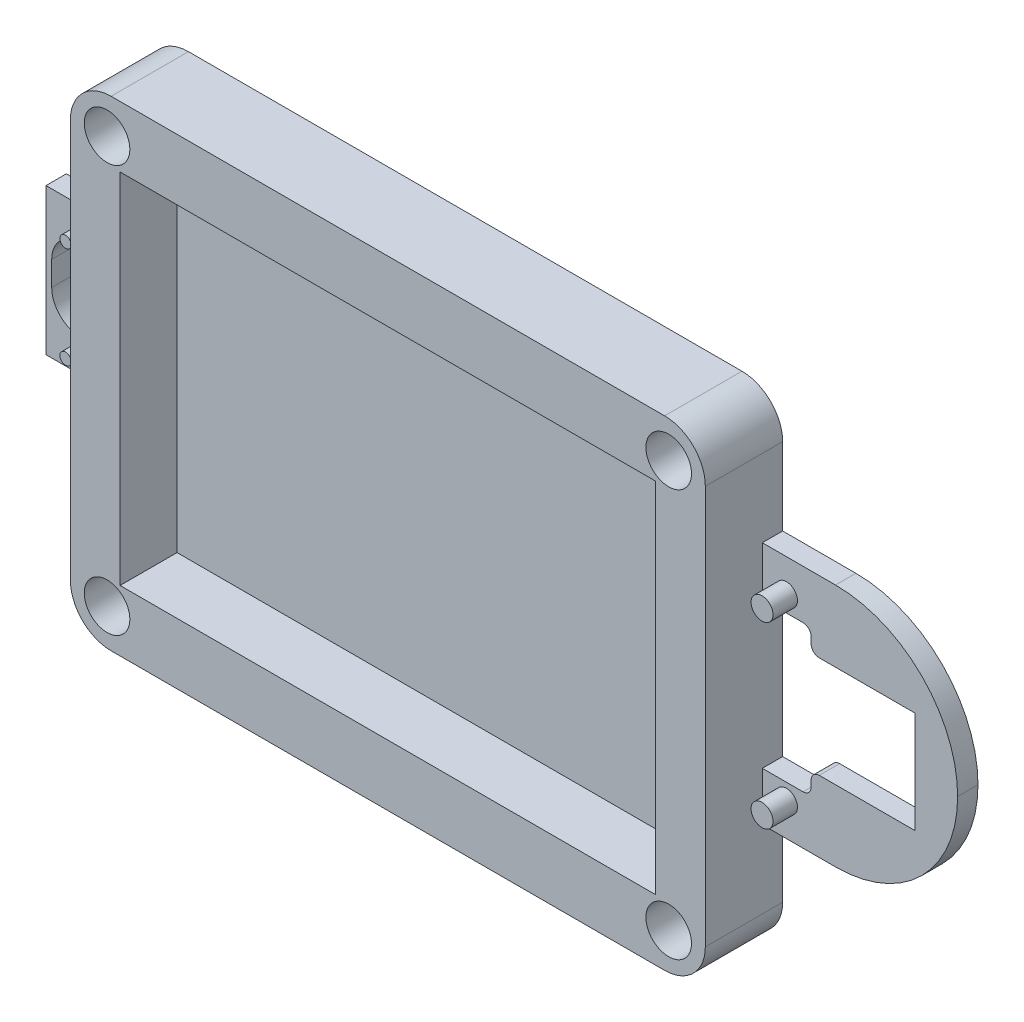
SolidWorks part; units mm, degrees
ref_plane "Front Plane" through (0, 0, 0) normal (1, 0, 0) x (0, 1, 0)
ref_plane "Top Plane" through (0, 0, 0) normal (0, 0, 1) x (0, 1, 0)
ref_plane "Right Plane" through (0, 0, 0) normal (0, 1, 0) x (-1, 0, 0)
sketch "Sketch1" plane through (0, 0, 0) normal (0, 0, 1) x (0, 1, 0)
  line L1 (-27.94, -41.783) -> (27.94, -41.783)
  line L2 (-27.94, -41.783) -> (-27.94, 41.783)
  line L3 (-27.94, 41.783) -> (27.94, 41.783)
  line L4 (27.94, -41.783) -> (27.94, 41.783)
  line L5 (-27.94, -41.783) -> (27.94, 41.783) construction
  line L6 (-27.94, 41.783) -> (27.94, -41.783) construction
  point P0 (0, 0)
  dimension "D1" = 55.88
  dimension "D2" = 83.566
extrude "Boss-Extrude1" add sketch "Sketch1" along normal blind 3.175
sketch "Sketch2" plane through (0, 0, 0) normal (0, 0, 1) x (0, 1, 0)
  line L8 (37.465, -51.308) -> (37.465, 51.308)
  line L9 (37.465, 51.308) -> (-37.465, 51.308)
  line L10 (-37.465, 51.308) -> (-37.465, -51.308)
  line L11 (-37.465, -51.308) -> (37.465, -51.308)
  line L12 (37.465, -51.308) -> (37.465, 51.308)
  line L13 (37.465, 51.308) -> (-37.465, 51.308)
  line L14 (-37.465, 51.308) -> (-37.465, -51.308)
  line L15 (-37.465, -51.308) -> (37.465, -51.308)
  line L16 (27.94, -41.783) -> (27.94, 41.783)
  line L17 (27.94, 41.783) -> (-27.94, 41.783)
  line L18 (-27.94, 41.783) -> (-27.94, -41.783)
  line L19 (-27.94, -41.783) -> (27.94, -41.783)
  line L20 (27.94, -41.783) -> (27.94, 41.783)
  line L21 (27.94, 41.783) -> (-27.94, 41.783)
  line L22 (-27.94, 41.783) -> (-27.94, -41.783)
  line L23 (-27.94, -41.783) -> (27.94, -41.783)
  dimension "D1" = 9.525
  dimension "D2" = 0
extrude "Boss-Extrude2" add sketch "Sketch2" along normal offset from surface (12.065 mm away) 8.89 contours L14 L15 L12 L13 L23 L22 L21 L20 region at (50.0374, 0, 0) up to face at (0, 0, 3.175) offset beyond the face yes
sketch "Sketch3" plane through (0, 0, 12.065) normal (0, 0, 1) x (1, 0, 0)
  line L0 (-43.815, 31.75) -> (43.815, 31.75) construction
  line L1 (-43.815, 31.75) -> (-43.815, -31.75) construction
  circle A0 centre (-43.815, 31.75) radius 3.556
  circle A1 centre (43.815, 31.75) radius 3.556
  circle A2 centre (43.815, -31.75) radius 3.556
  circle A3 centre (-43.815, -31.75) radius 3.556
  point P8 (0, 31.75)
  point P9 (-43.815, 0)
  dimension "D1" = 7.112
  dimension "D2" = 87.63
  dimension "D3" = 63.5
extrude "Cut-Extrude1" cut sketch "Sketch3" against normal through all both and the other way through all
sketch "Sketch4" plane through (0, 0, 12.065) normal (0, 0, 1) x (1, 0, 0)
  line L0 (-51.308, -37.465) -> (51.308, -37.465) construction
  line L1 (-51.308, 37.465) -> (-49.53, 37.465)
  line L2 (-51.308, 37.465) -> (-51.308, -37.465)
  line L3 (-51.308, -37.465) -> (-49.53, -37.465)
  line L4 (-49.53, 37.465) -> (-49.53, -37.465)
  line L5 (-47.371, 31.75) -> (-49.53, 31.75) construction
  line L6 (51.308, 37.465) -> (49.53, 37.465)
  line L7 (51.308, 37.465) -> (51.308, -37.465)
  line L8 (51.308, -37.465) -> (49.53, -37.465)
  line L9 (49.53, 37.465) -> (49.53, -37.465)
  line L10 (-43.815, 35.306) -> (-43.815, 37.465) construction
  line L11 (51.308, 37.465) -> (-51.308, 37.465) construction
  line L12 (-47.371, 31.75) -> (-43.815, 31.75) construction
  line L13 (-43.815, 35.306) -> (-43.815, 31.75) construction
  circle A0 centre (-43.815, 31.75) radius 3.556 construction
extrude "Cut-Extrude2" cut sketch "Sketch4" against normal through all both and the other way through all
fillet "Fillet1" radius 6.35 4 edges at (-49.53, -37.465, 6.0325) (-49.53, 37.465, 6.0325) (49.53, 37.465, 6.0325) (49.53, -37.465, 6.0325)
fillet "Fillet2" radius 0.508 4 edges at (-40.259, 31.75, 0) (47.371, 31.75, 0) (47.371, -31.75, 0) (-40.259, -31.75, 0)
sketch "Sketch5" plane through (49.53, 0, 0) normal (1, 0, 0) x (0, 1, 0)
  line L1 (-19.05, 3.175) -> (19.05, 3.175)
  line L2 (-19.05, 3.175) -> (-19.05, 0)
  line L3 (-19.05, 0) -> (19.05, 0)
  line L4 (19.05, 3.175) -> (19.05, 0)
  point P4 (0, 0)
  dimension "D1" = 3.175
  dimension "D2" = 38.1
extrude "Boss-Extrude3" add sketch "Sketch5" along normal blind 30.48
sketch "Sketch6" plane through (0, 0, 3.175) normal (0, 0, 1) x (1, 0, 0)
  line L0 (80.01, 19.05) -> (80.01, -19.05) construction
  line L1 (49.53, 11.43) -> (57.15, 11.43)
  line L2 (49.53, 11.43) -> (49.53, -11.43)
  line L3 (49.53, -11.43) -> (57.15, -11.43)
  line L4 (57.15, 11.43) -> (57.15, -11.43)
  line L5 (49.53, -31.115) -> (49.53, 31.115) construction
  point P8 (49.53, 0)
  point P9 (80.01, 0)
  dimension "D1" = 22.86
  dimension "D2" = 7.62
extrude "Cut-Extrude3" cut sketch "Sketch6" against normal through all both and the other way through all
sketch "Sketch7" plane through (0, 0, 3.175) normal (0, 0, 1) x (1, 0, 0)
  line L0 (53.3019, 13.9573) -> (53.3019, -13.9573) construction
  line L1 (49.53, 0) -> (80.01, 0) construction
  line L2 (49.53, -31.115) -> (49.53, 31.115) construction
  line L3 (80.01, 19.05) -> (80.01, -19.05) construction
  line L4 (49.53, 19.05) -> (49.53, 11.43) construction
  circle A0 centre (53.3019, 13.9573) radius 1.7145
  circle A1 centre (53.3019, -13.9573) radius 1.7145
  point P10 (53.3019, 0)
  dimension "D1" = 3.429
  dimension "D2" = 24.4856
  dimension "D3" = 2.0574
extrude "Boss-Extrude4" add sketch "Sketch7" along normal blind 3.81
sketch "Sketch8" plane through (0, 0, 3.175) normal (0, 0, 1) x (1, 0, 0)
  line L0 (80.01, 19.05) -> (80.01, -19.05) construction
  line L1 (80.01, 7.9375) -> (57.15, 7.9375)
  line L2 (80.01, 7.9375) -> (80.01, -7.9375)
  line L3 (80.01, -7.9375) -> (57.15, -7.9375)
  line L4 (57.15, 7.9375) -> (57.15, -7.9375)
  line L5 (57.15, 11.43) -> (57.15, -11.43) construction
  point P6 (57.15, 0)
  dimension "D1" = 15.875
extrude "Cut-Extrude4" cut sketch "Sketch8" against normal through all both and the other way through all
sketch "Sketch9" plane through (0, 0, 3.175) normal (0, 0, 1) x (1, 0, 0)
  line L0 (80.01, -7.9375) -> (57.15, -7.9375) construction
  line L1 (80.01, 7.9375) -> (73.3171, 7.9375)
  line L2 (80.01, 7.9375) -> (80.01, -7.9375)
  line L3 (80.01, -7.9375) -> (73.3171, -7.9375)
  line L4 (73.3171, 7.9375) -> (73.3171, -7.9375)
  line L5 (49.53, -31.115) -> (49.53, 31.115) construction
  dimension "D1" = 23.7871
extrude "Boss-Extrude5" add sketch "Sketch9" against normal up to surface (3.175 mm away) up to face at (-47.879, 31.75, 0)
fillet "Fillet3" radius 19.05 2 edges at (80.01, -19.05, 1.5875) (80.01, 19.05, 1.5875)
fillet "Fillet5" radius 1.27 4 edges at (57.15, 7.9375, 1.5875) (57.15, -7.9375, 1.5875) (57.15, -11.43, 1.5875) (57.15, 11.43, 1.5875)
sketch "Sketch10" plane through (-49.53, 0, 0) normal (-1, 0, 0) x (0, -1, 0)
  line L0 (-7.9375, 3.175) -> (7.9375, 3.175) construction
  line L1 (-11.43, 3.175) -> (11.43, 3.175)
  line L2 (-11.43, 3.175) -> (-11.43, 0)
  line L3 (-11.43, 0) -> (11.43, 0)
  line L4 (11.43, 3.175) -> (11.43, 0)
  line L5 (-7.9375, 3.175) -> (7.9375, 3.175) construction
  point P4 (0, 0)
  dimension "D2" = 22.86
extrude "Boss-Extrude6" add sketch "Sketch10" along normal blind 12.7
sketch "Sketch11" plane through (0, 0, 3.175) normal (0, 0, 1) x (1, 0, 0)
  line L0 (-49.53, 31.115) -> (-49.53, -31.115) construction
  line L1 (-52.9336, 7.4676) -> (-49.53, 7.4676)
  line L2 (-52.9336, 7.4676) -> (-52.9336, -7.4676)
  line L3 (-52.9336, -7.4676) -> (-49.53, -7.4676)
  line L4 (-49.53, 7.4676) -> (-49.53, -7.4676)
  point P4 (-49.53, 0)
  dimension "D1" = 3.4036
  dimension "D2" = 14.9352
extrude "Cut-Extrude5" cut sketch "Sketch11" against normal through all both and the other way through all
sketch "Sketch12" plane through (0, 0, 0) normal (0, 0, -1) x (1, 0, 0)
  line L0 (-56.896, 1.905) -> (-56.896, -1.905) construction
  line L1 (-52.451, 1.905) -> (-52.451, -1.905)
  line L2 (-61.341, 1.905) -> (-61.341, -1.905)
  line L5 (-49.53, 31.115) -> (-49.53, 11.43) construction
  arc A0 (-52.451, 1.905) -> (-61.341, 1.905) centre (-56.896, 1.905) ccw
  arc A1 (-61.341, -1.905) -> (-52.451, -1.905) centre (-56.896, -1.905) ccw
  point P2 (-56.896, 0)
  dimension "D1" = 12.7
  dimension "D2" = 8.89
  dimension "D3" = 11.811
extrude "Cut-Extrude6" cut sketch "Sketch12" against normal through all both and the other way through all
fillet "Fillet7" radius 0.508 2 edges
sketch "Sketch13" plane through (0, 0, 3.175) normal (0, 0, 1) x (1, 0, 0)
  line L0 (-56.642, 7.8994) -> (-56.642, -7.8994) construction
  line L1 (-49.53, 31.115) -> (-49.53, -31.115) construction
  circle A0 centre (-56.642, 7.8994) radius 0.889
  circle A1 centre (-56.642, -7.8994) radius 0.889
  point P4 (-56.642, 0)
  dimension "D1" = 14.0208
  dimension "D2" = 1.778
  dimension "D3" = 6.223
extrude "Boss-Extrude7" add sketch "Sketch13" along normal blind 2.54
